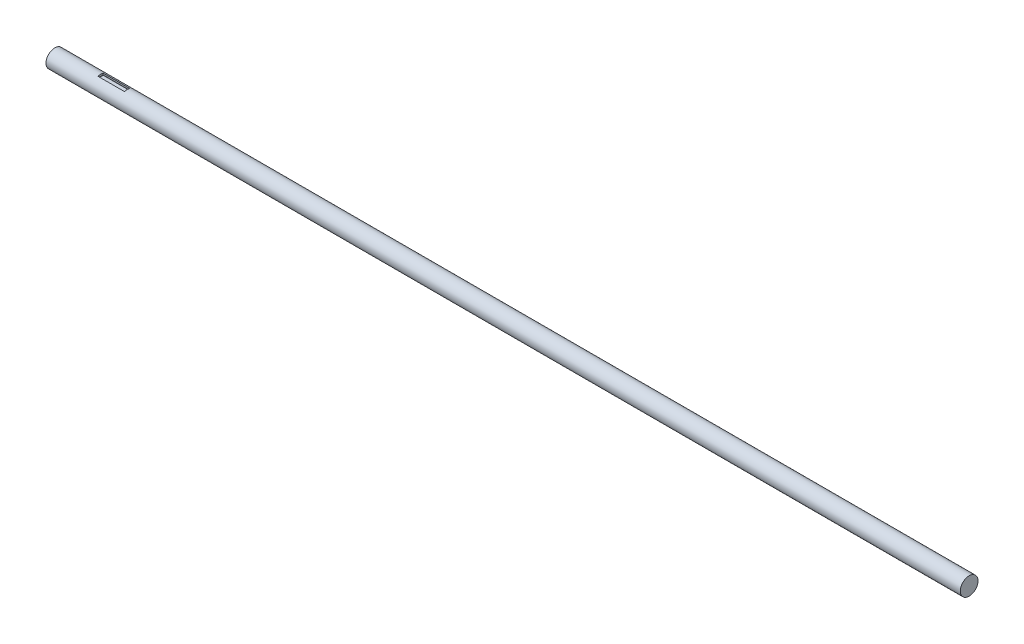
SolidWorks part; units mm, degrees
ref_plane "Front Plane" through (0, 0, 0) normal (0, 0, 1) x (1, 0, 0)
ref_plane "Top Plane" through (0, 0, 0) normal (0, 1, 0) x (1, 0, 0)
ref_plane "Right Plane" through (0, 0, 0) normal (1, 0, 0) x (0, 0, -1)
sketch "Sketch1" plane through (0, 0, 0) normal (1, 0, 0) x (0, 0, -1)
  circle A0 centre (0, 0) radius 30
  dimension "D1" = 60
extrude "Boss-Extrude1" add sketch "Sketch1" along normal blind 3100
ref_plane "Plane1" through (0, 30, 0) normal (0, 1, 0) x (1, 0, 0)
sketch "Sketch4" plane through (0, 30, 0) normal (0, 1, 0) x (1, 0, 0)
  line L0 (0, 30) -> (0, -30) construction
  line L1 (0, 30) -> (0, -30)
  line L3 (155, 9) -> (245, 9)
  line L4 (155, 9) -> (155, -9)
  line L5 (155, -9) -> (245, -9)
  line L6 (245, 9) -> (245, -9)
  line L7 (155, 9) -> (245, -9) construction
  line L8 (155, -9) -> (245, 9) construction
  point P2 (200, 0)
  point P7 (0, 0)
  point P8 (0, 0)
  point P12 (0, 0)
  dimension "D1" = 18
  dimension "D2" = 90
  dimension "D3" = 200
extrude "Cut-Extrude1" cut sketch "Sketch4" against normal blind 7 contours L6 L3 L4 L5 region at (200, 30, 0)
fillet "Fillet1" radius 0.6 4 edges at (200, 23, 9) (245, 23, 0) (155, 23, 0) (200, 23, -9)
